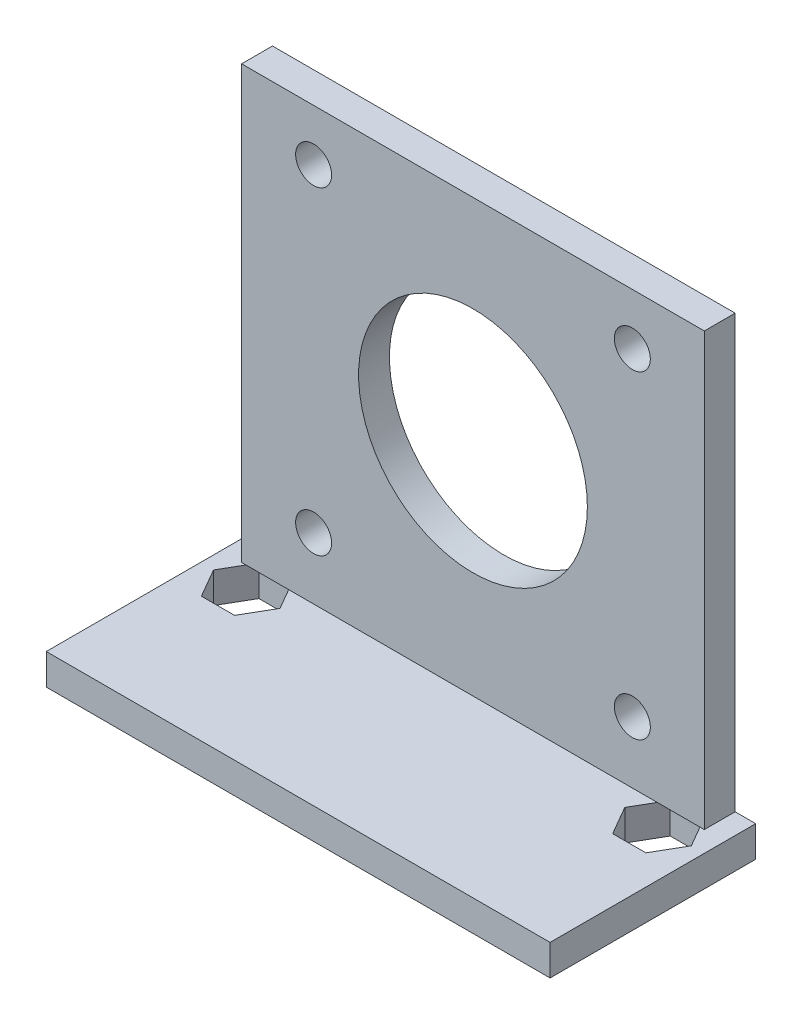
SolidWorks part; units mm, degrees
ref_plane "Plan de face" through (0, 0, 0) normal (0, 0, 1) x (1, 0, 0)
ref_plane "Plan de dessus" through (0, 0, 0) normal (0, 1, 0) x (1, 0, 0)
ref_plane "Plan de droite" through (0, 0, 0) normal (1, 0, 0) x (0, 0, -1)
sketch "Esquisse1" plane through (0, 0, 0) normal (0, 0, 1) x (1, 0, 0)
  line L0 (0, 31) -> (31, 0) construction
  line L1 (0, 31) -> (31, 31) construction
  line L2 (0, 31) -> (0, 0) construction
  line L3 (0, 0) -> (31, 0) construction
  line L4 (31, 31) -> (31, 0) construction
  line L5 (-7, 36) -> (38, 36)
  line L6 (-7, 36) -> (-7, -6)
  line L7 (-7, -6) -> (38, -6)
  line L8 (38, 36) -> (38, -6)
  circle A0 centre (0, 31) radius 1.75
  circle A1 centre (31, 31) radius 1.75
  circle A2 centre (31, 0) radius 1.75
  circle A3 centre (0, 0) radius 1.75
  circle A4 centre (15.5, 15.5) radius 11.125
  point P14 (0, 15.5)
  dimension "D5" = 3.5
  dimension "D6" = 22.25
  dimension "D1" = 5
  dimension "D2" = 7
  dimension "D3" = 6
  dimension "D4" = 31
  dimension "D7" = 7
extrude "Boss.-Extru.1" add sketch "Esquisse1" along normal blind 3
sketch "Esquisse3" plane through (0, -6, 0) normal (0, -1, 0) x (1, 0, 0)
  line L0 (-7, 20) -> (-9, 20)
  line L1 (-7, 0) -> (38, 0)
  line L2 (-7, 0) -> (-7, 20) construction
  line L3 (-7, 20) -> (38, 20)
  line L4 (38, 0) -> (38, 20) construction
  line L5 (-7, 3) -> (38, 3) construction
  line L6 (15.5, 20) -> (15.5, 3) construction
  line L7 (-1.2668, 5) -> (-2.8834, 7.8)
  line L8 (-2.8834, 7.8) -> (-6.1166, 7.8)
  line L9 (-6.1166, 7.8) -> (-7.7332, 5)
  line L10 (-7.7332, 5) -> (-6.1166, 2.2)
  line L11 (-6.1166, 2.2) -> (-2.8834, 2.2)
  line L12 (-2.8834, 2.2) -> (-1.2668, 5)
  line L13 (-9, 20) -> (-9, 0)
  line L14 (-9, 0) -> (-7, 0)
  line L15 (33.8834, 2.2) -> (32.2668, 5)
  line L16 (37.1166, 2.2) -> (33.8834, 2.2)
  line L17 (38.7332, 5) -> (37.1166, 2.2)
  line L18 (37.1166, 7.8) -> (38.7332, 5)
  line L19 (33.8834, 7.8) -> (37.1166, 7.8)
  line L20 (32.2668, 5) -> (33.8834, 7.8)
  line L21 (40, 0) -> (38, 0)
  line L22 (38, 20) -> (40, 20)
  line L23 (40, 20) -> (40, 0)
  circle A3 centre (-4.5, 5) radius 2.8 construction
  dimension "D2" = 15
  dimension "D3" = 2
  dimension "D5" = 5.6
  dimension "D1" = 20
  dimension "D4" = 20
extrude "Boss.-Extru.2" add sketch "Esquisse3" along normal blind 3
equation "\"D2@Esquisse1\"=\"D1@Esquisse1\""
